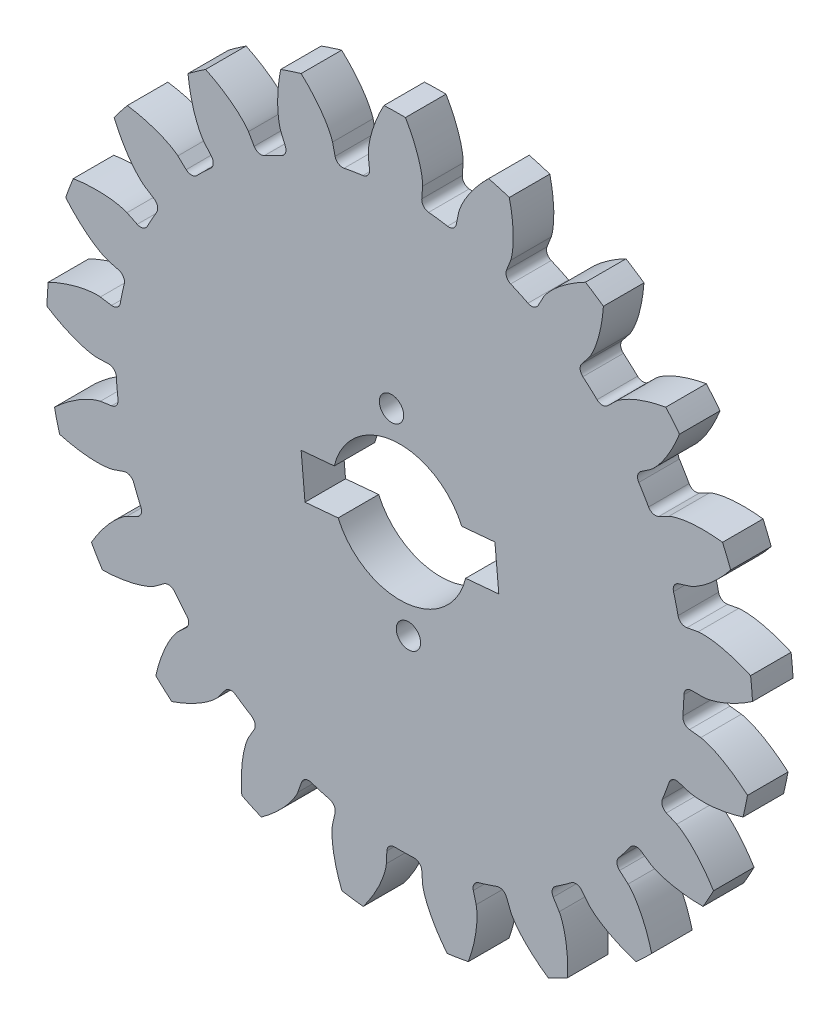
SolidWorks part; units mm, degrees
material "Acrylic (Medium-high impact)"
ref_plane "Front Plane" through (0, 0, 0) normal (0, 0, 1) x (1, 0, 0)
ref_plane "Top Plane" through (0, 0, 0) normal (0, 1, 0) x (1, 0, 0)
ref_plane "Right Plane" through (0, 0, 0) normal (1, 0, 0) x (0, 0, -1)
sketch "Sketch1" plane through (0, 0, 0) normal (0, 0, 1) x (1, 0, 0)
  line L0 (22.4242, 0) -> (21.0225, 0)
  line L1 (26.031, 2.3414) -> (-26.031, -2.3414)
  line L2 (0, 0) -> (23.8607, 0.3557) construction
  circle A0 centre (0, 0) radius 22.4242 construction
  circle A1 centre (0, 0) radius 26.1361
  circle A2 centre (0, 0) radius 21.0225
  circle A3 centre (0, 0) radius 23.8634 construction
  spline S0 degree 4 poles (22.4242, 0) (22.4408, 0.0004) (22.4873, 0.0024) (22.5749, 0.0106) (22.7173, 0.0301) (22.8977, 0.0637) (23.1291, 0.1173) (23.3991, 0.1934) (23.6926, 0.2905) (24.0079, 0.4104) (24.3185, 0.5426) (24.6242, 0.6859) (24.925, 0.8391) (25.284, 1.0363) (25.7079, 1.29) (26.1909, 1.6087) (26.7258, 1.9997) (27.2523, 2.4235) (27.7593, 2.8681) (28.2491, 3.335) (28.7183, 3.817) (29.1733, 4.3219) (29.5495, 4.7676) (29.8707, 5.1742) (30.1155, 5.4944) (30.3334, 5.795) (30.5423, 6.0843) (30.8755, 6.5807) (31.0773, 6.8936) (31.3811, 7.3873) (31.4857, 7.5713) (31.5713, 7.7174) knots 0 0 0 0 0 0.005377 0.015084 0.028532 0.04661 0.064855 0.092111 0.119476 0.146842 0.174209 0.201575 0.228941 0.256307 0.307035 0.361767 0.4165 0.471232 0.525964 0.580697 0.635429 0.690161 0.744894 0.77226 0.799626 0.826992 0.854358 0.909091 0.954545 1 1 1 1 1 construction
  spline S1 degree 4 poles (22.4242, 0) (22.4408, 0.0004) (22.4873, 0.0024) (22.5749, 0.0106) (22.7173, 0.0301) (22.8977, 0.0637) (23.1291, 0.1173) (23.3991, 0.1934) (23.6926, 0.2905) (24.0079, 0.4104) (24.3185, 0.5426) (24.6242, 0.6859) (24.925, 0.8391) (25.284, 1.0363) (25.7079, 1.29) (26.1909, 1.6087) (26.7258, 1.9997) (27.2523, 2.4235) (27.7593, 2.8681) (28.2491, 3.335) (28.7183, 3.817) (29.1733, 4.3219) (29.5495, 4.7676) (29.8707, 5.1742) (30.1155, 5.4944) (30.3334, 5.795) (30.5423, 6.0843) (30.7777, 6.4351) (30.9023, 6.6244) (30.9852, 6.7535) knots 0 0 0 0 0 0.005377 0.015084 0.028532 0.04661 0.064855 0.092111 0.119476 0.146842 0.174209 0.201575 0.228941 0.256307 0.307035 0.361767 0.4165 0.471232 0.525964 0.580697 0.635429 0.690161 0.744894 0.77226 0.799626 0.826992 0.854358 0.909091 0.909091 0.909091 0.909091 0.909091
  dimension "D1" = 44.8484
  dimension "D2" = 52.2721
  dimension "D3" = 42.045
  dimension "D5" = 47.7267
  dimension "D4" = 4.286
extrude "Boss-Extrude3" add sketch "Sketch1" along normal blind 3 contours L1 A2 | A2 L1 | L0 S1 A1 L1 A2
mirror "Mirror2" about plane through (0, 0, 3) normal (0.0896, -0.996, 0) of "Boss-Extrude3"
fillet "Fillet1" radius 0.5682 2 edges at (20.6851, 3.7514, 1.5) (21.0225, 0, 1.5)
pattern_circular "CirPattern8" count 21 over 360 about axis through (0, 0, 3) along (0, 0, -1) of "Boss-Extrude3", "Mirror2", "Fillet1"
sketch "Sketch3" plane through (0, 0, 3) normal (0, 0, 1) x (1, 0, 0)
  circle A0 centre (0, 0) radius 5
  dimension "D1" = 10
extrude "Cut-Extrude2" cut sketch "Sketch3" against normal through all
sketch "Sketch6" plane through (0, 0, 3) normal (0, 0, 1) x (1, 0, 0)
  line L0 (26.031, 2.3414) -> (-26.031, -2.3414) construction
  line L1 (0, 0) -> (4.9799, 0.4479) construction
  line L2 (4.9799, 0.4479) -> (7.1711, 0.645) construction
  line L3 (4.8614, -1.1692) -> (7.3144, -0.9486)
  line L4 (7.3144, -0.9486) -> (7.0277, 2.2386)
  line L5 (7.0277, 2.2386) -> (4.5747, 2.0179)
  line L6 (26.031, 2.3414) -> (-26.031, -2.3414) construction
  circle A1 centre (0, 0) radius 5 construction
  arc A2 (4.5747, 2.0179) -> (4.8614, -1.1692) centre (0, 0) cw
  dimension "D1" = 3.2
  dimension "D2" = 2.2
extrude "Cut-Extrude4" cut sketch "Sketch6" against normal through all
pattern_circular "CirPattern10" [suppressed] count 2 over 360
sketch "Sketch7" plane through (0, 0, 3) normal (0, 0, 1) x (1, 0, 0)
  line L0 (0, 0) -> (7.1711, 0.645) construction
  line L1 (7.3144, -0.9486) -> (7.0277, 2.2386) construction
  line L2 (0, 0) -> (-0.6271, 6.9719) construction
  circle A0 centre (0, 0) radius 7 construction
  circle A1 centre (-0.6271, 6.9719) radius 0.9
  dimension "D1" = 1.8
  dimension "D2" = 14
extrude "Cut-Extrude5" cut sketch "Sketch7" against normal through all
pattern_circular "CirPattern11" count 2 over 360 about axis through (0, 0, 0) along (0, 0, 1) of "Cut-Extrude5", "Cut-Extrude4"
equation "\"d\"= \"Module\" * \"Num_Teeth\"'Pitch diameter"
equation "\"Num_Teeth\"= 21"
equation "\"bl\"= 0'Backlash"
equation "\"pa\"= 20deg'Pressure angle (deg)"
equation "\"pc\"= ( 3.1415 * \"d\" ) / \"Num_Teeth\"\t'Circular pitch"
equation "\"Module\"= 2.2727"
equation "\"P\"= \"Num_Teeth\" / \"d\"\t\t\t'Diametral pitch"
equation "\"a\"= 1/\"P\"\t\t\t'Addendum distance"
equation "\"b\"= 1.25 / \"P\"'Dedendum distance"
equation "\"rb\"= (\"d\"/2)*cos(\"pa\")\t\t'base circle radius"
equation "\"cp\"= 3.1415/\"P\"\t\t'Circular pitch"
equation "\"t\"= ( \"cp\" / 2 ) - \"bl\"'tooth tickness"
equation "\"c\"=\"b\"-\"a\"\t\t\t'Clearance"
equation "\"Facewidth\"= 3"
equation "\"rbd\"= \"rb\" * 2'base circle diameter"
equation "\"D1@Sketch1\"=\"rbd\""
equation "\"D2@Sketch1\"=\"d\" + (\"a\" * 2)"
equation "\"D3@Sketch1\" = \"ded\""
equation "\"D4@Sketch1\"= ((\"t\" /2) / (\"d\"/2)) * (180/3.1415)"
equation "\"D1@Boss-Extrude3\"=\"Facewidth\""
equation "\"D1@Fillet1\"=\"c\""
equation "\"D1@CirPattern8\"=\"Num_Teeth\""
equation "\"D5@Sketch1\"=\"d\""
equation "\"ded1\"= \"d\" - 2 * ( ( ( \"d\" / 2 ) - \"rb\" ) + ( 0.5 * ( 1.25 / \"P\" ) ) )"
equation "\"ded2\"= \"d\" - ( \"b\" * 2 )"
equation "\"ded\"= IIF ( \"rb\" < ( \"ded2\" / 2 ) , \"ded1\" , \"ded2\" )"
equation "\"Shaft_Diameter\"=10"
equation "\"D1@Sketch3\"=\"Shaft_Diameter\""
equation "\"Key_Width\"= 3.2"
equation "\"Key_Number\"=2"
equation "\"Key_Number@CirPattern10\"= \"Key_Number\""
equation "\"D1@Sketch6\"=\"Key_Width\""
equation "\"Key_Height\"= 2.2"
equation "\"D2@Sketch6\"=\"Key_Height\""
equation "\"Alignment_Pin_Diameter\"=1.8"
equation "\"Alignment_Pin_Circle_Diameter\"=14"
equation "\"D1@Sketch7\"=\"Alignment_Pin_Diameter\""
equation "\"D2@Sketch7\"=\"Alignment_Pin_Circle_Diameter\""
